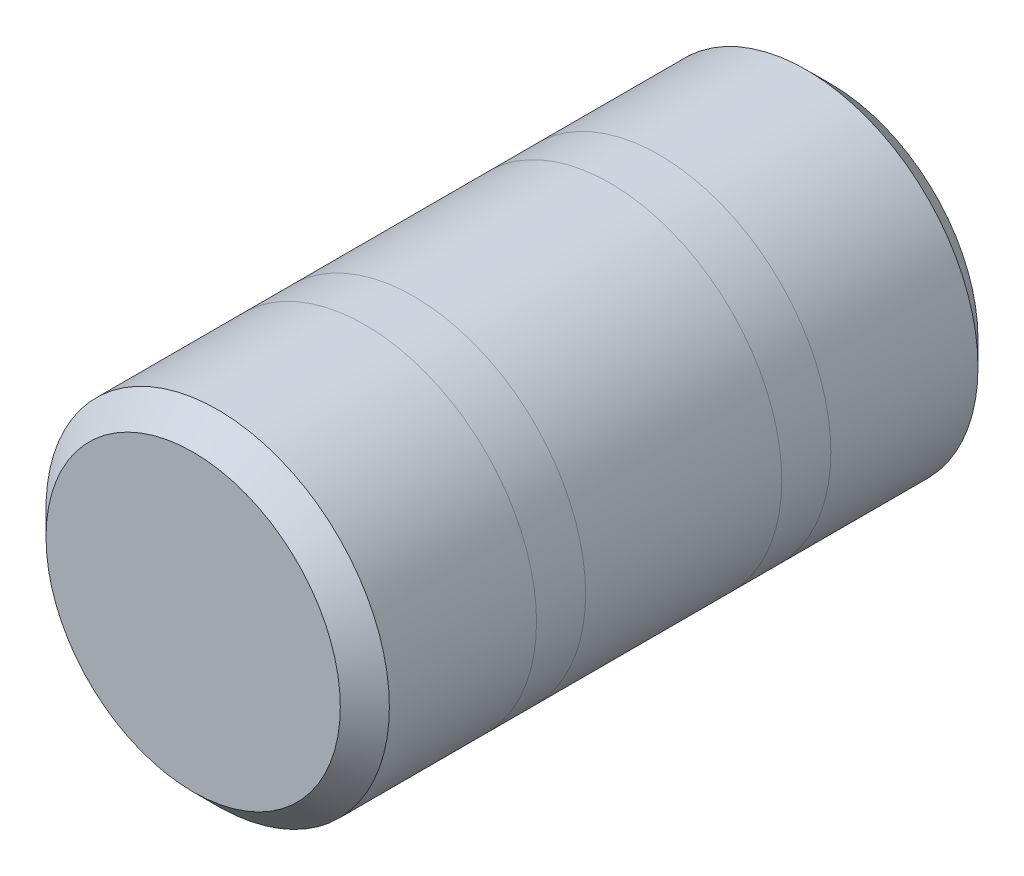
SolidWorks part; units mm, degrees
material "Low alloy steel, AISI 4340, normalized"
ref_plane "Front Plane" through (0, 0, 0) normal (0, 0, 1) x (1, 0, 0)
ref_plane "Top Plane" through (0, 0, 0) normal (0, 1, 0) x (1, 0, 0)
ref_plane "Right Plane" through (0, 0, 0) normal (1, 0, 0) x (0, 0, -1)
sketch "Sketch1" plane through (0, 0, 0) normal (0, 0, 1) x (1, 0, 0)
  circle A0 centre (0, 0) radius 17.5
  dimension "D1" = 35
extrude "Boss-Extrude1" add sketch "Sketch1" along normal blind 65
sketch "Sketch2" plane through (0, 0, 65) normal (0, 0, 1) x (1, 0, 0)
  circle A0 centre (0, 0) radius 10
  dimension "D1" = 20
extrude "Cut-Extrude1" [suppressed] cut sketch "Sketch2" against normal through all both and the other way through all
chamfer "Chamfer1" distance 2.5 angle 45 2 edges at (17.5, 0, 65) (17.5, 0, 0)
ref_plane "Plane1" through (0, 0, 42.5) normal (0, 0, 1) x (1, 0, 0)
ref_plane "Plane2" through (0, 0, 22.5) normal (0, 0, 1) x (1, 0, 0)
ref_plane "Plane3" through (0, 0, 17.5) normal (0, 0, 1) x (1, 0, 0)
ref_plane "Plane4" through (0, 0, 2.5) normal (0, 0, 1) x (1, 0, 0)
ref_plane "Plane5" through (0, 0, 47.5) normal (0, 0, 1) x (1, 0, 0)
ref_plane "Plane6" through (0, 0, 62.5) normal (0, 0, 1) x (1, 0, 0)
split line "Split Line2"
split line "Split Line3"
split line "Split Line4"
split line "Split Line5"
